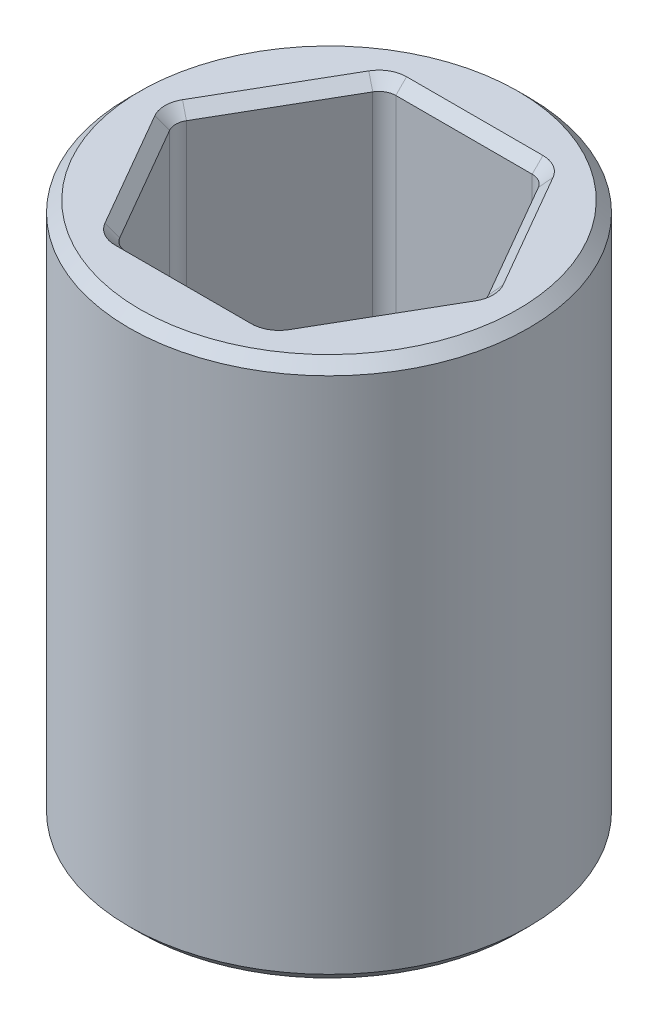
SolidWorks part; units mm, degrees
ref_plane "Front" through (0, 0, 0) normal (0, 0, 1) x (1, 0, 0)
ref_plane "Top" through (0, 0, 0) normal (0, 1, 0) x (1, 0, 0)
ref_plane "Right" through (0, 0, 0) normal (1, 0, 0) x (0, 0, -1)
sketch "Sketch4" plane through (0, 0, 0) normal (0, 1, 0) x (1, 0, 0)
  circle A0 centre (0, 0) radius 4.699
  circle A1 centre (0, 0) radius 1.5875
  dimension "D1" = 9.398
  dimension "D2" = 3.175
extrude "Boss-Extrude1" add sketch "Sketch4" along normal blind 12.7
sketch "Sketch7" plane through (0, 0, 0) normal (0, -1, 0) x (1, 0, 0)
  line L1 (1.6498, 2.8575) -> (-1.6498, 2.8575)
  line L2 (-1.6498, 2.8575) -> (-3.2996, 0)
  line L3 (-3.2996, 0) -> (-1.6498, -2.8575)
  line L4 (-1.6498, -2.8575) -> (1.6498, -2.8575)
  line L5 (1.6498, -2.8575) -> (3.2996, 0)
  line L6 (3.2996, 0) -> (1.6498, 2.8575)
  circle A0 centre (0, 0) radius 2.8575 construction
  dimension "D1" = 5.715
extrude "Cut-Extrude3" cut sketch "Sketch7" against normal blind 3.175
ref_plane "Plane1" through (0, 6.35, 0) normal (0, -1, 0) x (-1, 0, 0)
sketch "Sketch6" plane through (0, 12.7, 0) normal (0, 1, 0) x (1, 0, 0)
  line L1 (1.8331, 3.175) -> (-1.8331, 3.175)
  line L2 (-1.8331, 3.175) -> (-3.6662, 0)
  line L3 (-3.6662, 0) -> (-1.8331, -3.175)
  line L4 (-1.8331, -3.175) -> (1.8331, -3.175)
  line L5 (1.8331, -3.175) -> (3.6662, 0)
  line L6 (3.6662, 0) -> (1.8331, 3.175)
  circle A0 centre (0, 0) radius 3.175 construction
  dimension "D1" = 6.35
extrude "Cut-Extrude2" cut sketch "Sketch6" against normal up to surface (6.35 mm away) up to plane "Plane1"
fillet "Fillet1-1/64" radius 0.3969 24 edges at (-2.7496, 6.35, 1.5875) (0, 6.35, 3.175) (2.7496, 6.35, 1.5875) (2.7496, 6.35, -1.5875) (0, 6.35, -3.175) (-2.7496, 6.35, -1.5875) (-3.6662, 9.525, 0) (-1.8331, 9.525, 3.175) (1.8331, 9.525, 3.175) (3.6662, 9.525, 0) (1.8331, 9.525, -3.175) (-1.8331, 9.525, -3.175) (0, 3.175, 2.8575) (-2.4747, 3.175, 1.4287) (-2.4747, 3.175, -1.4288) (0, 3.175, -2.8575) (2.4747, 3.175, -1.4287) (2.4747, 3.175, 1.4288) (-1.6498, 1.5875, 2.8575) (-3.2996, 1.5875, 0) (-1.6498, 1.5875, -2.8575) (1.6498, 1.5875, -2.8575) (3.2996, 1.5875, 0) (1.6498, 1.5875, 2.8575)
chamfer "Chamfer1" distance 0.254 angle 45 28 edges at (0, 6.35, -1.5875) (-2.7496, 12.7, -1.5875) (-3.6048, 12.7, 0) (-1.8024, 12.7, -3.1218) (-2.7496, 12.7, 1.5875) (0, 12.7, -3.175) (-1.8024, 12.7, 3.1218) (1.8024, 12.7, -3.1218) (0, 12.7, 3.175) (2.7496, 12.7, -1.5875) (1.8024, 12.7, 3.1218) (3.6048, 12.7, 0) (2.7496, 12.7, 1.5875) (0, 12.7, 4.699) (0, 3.175, -1.5875) (-2.4747, 0, -1.4288) (-1.6191, 0, -2.8043) (-3.2382, 0, 0) (0, 0, -2.8575) (-2.4747, 0, 1.4287) (1.6191, 0, -2.8043) (-1.6191, 0, 2.8043) (2.4747, 0, -1.4287) (0, 0, 2.8575) (3.2382, 0, 0) (1.6191, 0, 2.8043) (2.4747, 0, 1.4288) (0, 0, 4.699)
